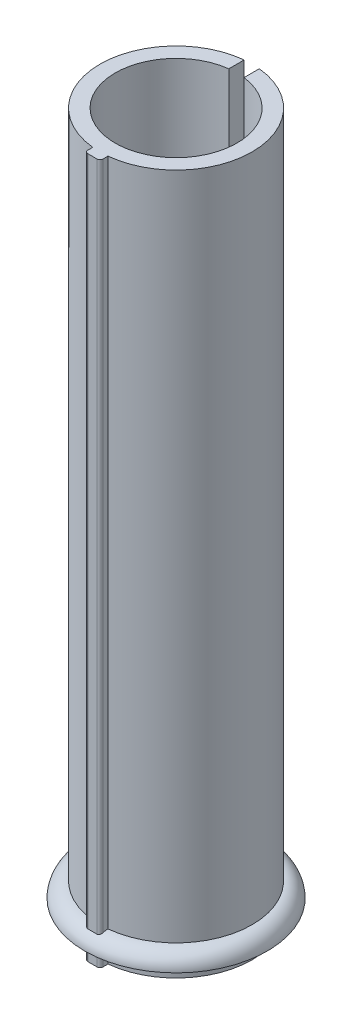
SolidWorks part; units mm, degrees
ref_plane "Front Plane" through (0, 0, 0) normal (0, 0, 1) x (1, 0, 0)
ref_plane "Top Plane" through (0, 0, 0) normal (0, 1, 0) x (1, 0, 0)
ref_plane "Right Plane" through (0, 0, 0) normal (1, 0, 0) x (0, 0, -1)
sketch "Sketch1" plane through (0, 0, 0) normal (0, 1, 0) x (1, 0, 0)
  line L0 (0, 0) -> (0, -22.5) construction
  line L1 (0, -27.5) -> (0, -36.5063) construction
  line L3 (-2.5, -24.8747) -> (-2.5, -26.5)
  line L4 (-1.5, -27.5) -> (1.5, -27.5)
  line L5 (2.5, -24.8747) -> (2.5, -26.5)
  line L8 (-2.5, 19.8431) -> (-2.5, 24.8747)
  line L10 (2.5, 19.8431) -> (2.5, 24.8747)
  arc A0 (2.5, -24.8747) -> (2.5, 24.8747) centre (0, 0) ccw
  arc A1 (-2.5, 19.8431) -> (2.5, 19.8431) centre (0, 0) ccw
  arc A2 (1.5, -27.5) -> (2.5, -26.5) centre (1.5, -26.5) ccw
  arc A3 (-2.5, -26.5) -> (-1.5, -27.5) centre (-1.5, -26.5) ccw
  arc A4 (-2.5, 24.8747) -> (-2.5, -24.8747) centre (0, 0) ccw
  point P11 (2.5, -27.5)
  point P14 (-2.5, -27.5)
  dimension "D1" = 50
  dimension "D2" = 40
  dimension "D7" = 1
  dimension "D3" = 27.5
  dimension "D5" = 5
  dimension "D6" = 2.5
extrude "Boss-Extrude1" add sketch "Sketch1" along normal blind 225 and the other way blind 5
sketch "Sketch2" plane through (0, 0, 0) normal (0, 1, 0) x (1, 0, 0)
  arc A0 (-30, 0) -> (16.5831, -25) centre (0, 0) ccw
  circle A1 centre (0, 0) radius 20
  arc A2 (16.5831, -25) -> (-30, 0) centre (0, 0) ccw
  dimension "D1" = 60
extrude "Boss-Extrude2" add sketch "Sketch2" along normal blind 5
sketch "Sketch6" plane through (0, 5, 0) normal (0, 1, 0) x (1, 0, 0)
  circle A0 centre (33, -6) radius 4.826
  circle A1 centre (-33, -6) radius 4.826
  circle A2 centre (-33, -6) radius 2.413
  circle A3 centre (33, -6) radius 2.413
  dimension "D1" = 9.652
  dimension "D2" = 9.652
  dimension "D3" = 4.826
  dimension "D4" = 4.826
  dimension "D5" = 33
  dimension "D6" = 6
  dimension "D7" = 6
  dimension "D8" = 33
extrude "Boss-Extrude6" [suppressed] add sketch "Sketch6" against normal blind 5 and the other way blind 6.1
sketch "Sketch7" [suppressed] plane through (0, 5, 0) normal (0, 1, 0) x (1, 0, 0)
  line L0 (-33, -6) -> (-33, 1.0603) construction
  line L1 (-29.279, -4.75) -> (-22.5949, -4.75)
  line L2 (-29.279, -4.75) -> (-29.279, -7.25)
  line L3 (-29.279, -7.25) -> (-22.5949, -7.25)
  line L4 (-22.5949, -4.75) -> (-22.5949, -7.25)
  line L5 (-33, 1.0603) -> (-40.0603, -6) construction
  line L6 (-40.0603, -6) -> (-33, -6) construction
  line L7 (0, 0) -> (0, -5.501) construction
  line L8 (29.279, -7.25) -> (22.5949, -7.25)
  line L9 (22.5949, -4.75) -> (22.5949, -7.25)
  line L10 (29.279, -4.75) -> (22.5949, -4.75)
  line L11 (29.279, -4.75) -> (29.279, -7.25)
  dimension "D1" = 2.5
  dimension "D2" = 1.25
extrude "Boss-Extrude7" [suppressed] add sketch "Sketch7" along normal up to surface (6.1 mm away)
fillet "Fillet3" radius 5 1 edges at (0, 5, 30)
sketch "Sketch8" plane through (0, 225, 0) normal (0, 1, 0) x (1, 0, 0)
  line L0 (-2.5, 24.8747) -> (-2.5, 19.8431)
  line L1 (-2.5, 19.8431) -> (2.5, 19.8431)
  line L2 (2.5, 19.8431) -> (2.5, 24.8747)
  arc A0 (-2.5, 24.8747) -> (2.5, 24.8747) centre (0, 0) ccw
extrude "Boss-Extrude8" [suppressed] add sketch "Sketch8" against normal blind 5
